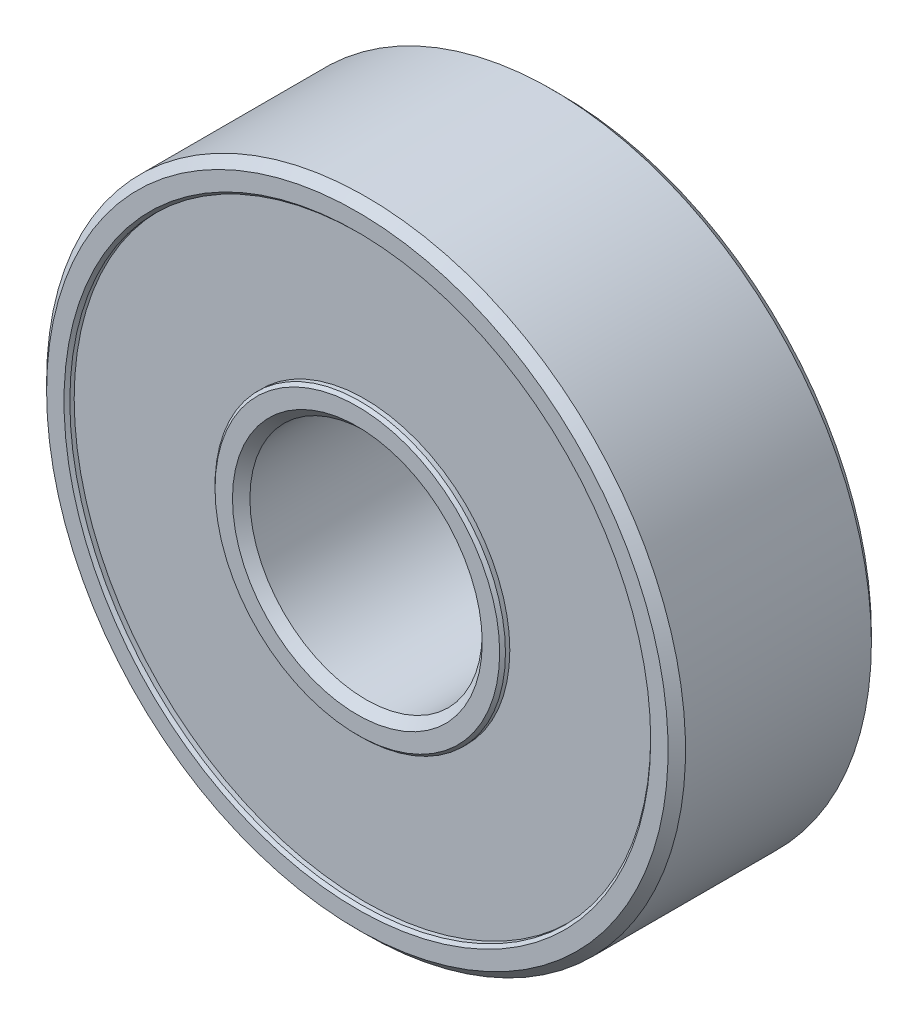
SolidWorks part; units mm, degrees
material "Plain Carbon Steel"
ref_plane "Front Plane" through (0, 0, 0) normal (0, 0, 1) x (1, 0, 0)
ref_plane "Top Plane" through (0, 0, 0) normal (0, 1, 0) x (1, 0, 0)
ref_plane "Right Plane" through (0, 0, 0) normal (1, 0, 0) x (0, 0, -1)
sketch "Sketch1" plane through (0, 0, 0) normal (0, 0, 1) x (1, 0, 0)
  circle A0 centre (0, 0) radius 11
  circle A1 centre (0, 0) radius 4
  circle A2 centre (0, 0) radius 5
  circle A3 centre (0, 0) radius 10
  dimension "D1" = 22
  dimension "D2" = 8
  dimension "D3" = 1
  dimension "D4" = 1
extrude "Boss-Extrude1" add sketch "Sketch1" along normal mid plane 7 contours A0 A3 | A2 A1 region at (-10.6889, 0, 0) region at (-4.8586, 0, 0)
extrude "Boss-Extrude2" add sketch "Sketch1<3>" along normal mid plane 6.5 contours A3 A2 region at (-9.7172, 0, 0)
sketch "Sketch1<3>" plane through (0, 0, 0) normal (0, 0, 1) x (1, 0, 0) same geometry as "Sketch1"
chamfer "Chamfer1" distance 0.3 angle 45 4 edges at (4, 0, -3.5) (11, 0, 3.5) (11, 0, -3.5) (4, 0, 3.5)
chamfer "Chamfer2" distance 0.1 angle 45 4 edges at (10, 0, 3.5) (5, 0, 3.5) (5, 0, -3.5) (10, 0, -3.25)
